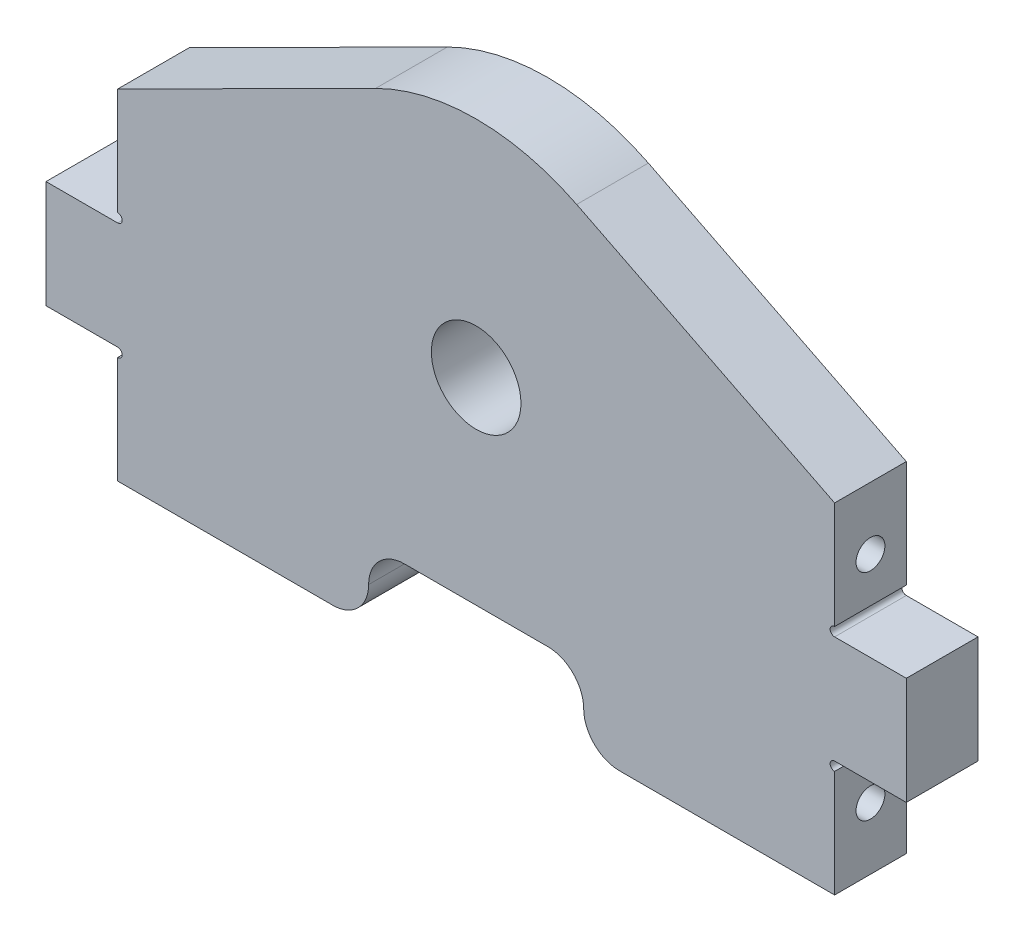
SolidWorks part; units mm, degrees
material "6061-T6 (SS)"
ref_plane "Front Plane" through (0, 0, 0) normal (0, 0, 1) x (1, 0, 0)
ref_plane "Top Plane" through (0, 0, 0) normal (0, 1, 0) x (1, 0, 0)
ref_plane "Right Plane" through (0, 0, 0) normal (1, 0, 0) x (0, 0, -1)
sketch "Sketch1" plane through (0, 0, 0) normal (0, 0, 1) x (1, 0, 0)
  line L1 (-63.5, 0) -> (63.5, 0)
  line L2 (-63.5, 0) -> (-63.5, 152.4)
  line L3 (-63.5, 152.4) -> (63.5, 152.4)
  line L4 (63.5, 0) -> (63.5, 152.4)
  dimension "D1" = 127
  dimension "D2" = 152.4
extrude "Boss-Extrude1" add sketch "Sketch1" along normal blind 12.7
sketch "Sketch2" plane through (0, 0, 12.7) normal (0, 0, 1) x (1, 0, 0)
  line L0 (-63.5, 56.977) -> (-17.8077, 79.9181)
  line L1 (-63.5, 152.4) -> (-63.5, 0) construction
  line L2 (-76.2, 56.977) -> (-63.5, 56.977) construction
  line L3 (63.5, 56.977) -> (17.8077, 79.9181)
  line L4 (63.5, 0) -> (63.5, 152.4) construction
  line L5 (63.5, 56.977) -> (76.2, 56.977) construction
  line L6 (-63.5, 56.977) -> (-63.5, 152.4)
  line L7 (-63.5, 152.4) -> (63.5, 152.4)
  line L8 (63.5, 152.4) -> (63.5, 56.977)
  circle A0 centre (0, 44.45) radius 7.9375
  circle A1 centre (0, 44.45) radius 39.6875
  line M1 (-63.5, 152.4) -> (-63.5, 0)
  line M3 (63.5, 0) -> (63.5, 152.4)
  line M4 (63.5, 152.4) -> (-63.5, 152.4)
  dimension "D1" = 79.375
extrude "Cut-Extrude1" cut sketch "Sketch2" against normal through all contours A1 L3 L0 M3 M4 M1 | A0 region at (0, 111.9722, 12.7) region at (0, 44.45, 12.7)
sketch "Sketch3" plane through (0, 0, 0) normal (0, 0, -1) x (-1, 0, 0)
  line L1 (-63.5, 0) -> (63.5, 0)
  line L2 (-63.5, 0) -> (-63.5, -3.175)
  line L3 (-63.5, -3.175) -> (63.5, -3.175)
  line L4 (63.5, 0) -> (63.5, -3.175)
extrude "Boss-Extrude2" add sketch "Sketch3" against normal blind 12.7
sketch "Sketch4" plane through (0, 0, 12.7) normal (0, 0, 1) x (1, 0, 0)
  line L0 (63.5, -3.175) -> (-63.5, -3.175) construction
  line L1 (-19.05, -3.175) -> (19.05, -3.175)
  line L2 (-19.05, -3.175) -> (-19.05, 9.525)
  line L3 (-19.05, 9.525) -> (19.05, 9.525)
  line L4 (19.05, -3.175) -> (19.05, 9.525)
  line L5 (63.5, -3.175) -> (63.5, 56.977) construction
  line L6 (-63.5, 56.977) -> (-63.5, -3.175) construction
  dimension "D1" = 44.45
  dimension "D2" = 44.45
  dimension "D3" = 12.7
extrude "Cut-Extrude2" cut sketch "Sketch4" against normal through all
fillet "Fillet1" radius 6.35 4 edges at (-19.05, -3.175, 6.35) (-19.05, 9.525, 6.35) (19.05, 9.525, 6.35) (19.05, -3.175, 6.35)
hole_wizard "1/4-20 Tapped Hole1" positions "Sketch6" profile "Sketch5" tap size "1/4-20" standard "ANSI Inch"
sketch "Sketch6" plane through (63.5, 0, 0) normal (1, 0, 0) x (0, 0, -1)
  line L0 (0, 26.901) -> (-6.35, 26.901) construction
  line L1 (0, -3.175) -> (0, 56.977) construction
  line L2 (-6.35, 26.901) -> (-6.35, 45.951) construction
  line L3 (-6.35, 45.951) -> (-6.35, 56.977) construction
  line L4 (0, 56.977) -> (-12.7, 56.977) construction
  line L5 (-6.35, 56.977) -> (-12.7, 26.901) construction
  line L6 (-12.7, -3.175) -> (-12.7, 56.977) construction
  line L7 (-12.7, 26.901) -> (-6.35, -3.175) construction
  line L8 (-12.7, -3.175) -> (0, -3.175) construction
  line L9 (-6.35, -3.175) -> (-6.35, 7.851) construction
  line L10 (-6.35, 7.851) -> (-6.35, 26.901) construction
  point P6 (-6.35, 45.951)
  point P20 (-6.35, 7.851)
  dimension "D1" = 19.05
sketch "Sketch5" plane through (63.5, 45.951, 6.35) normal (0, 1, 0) x (0, 0, -1)
  line L0 (0, 0) -> (0, 18.0438)
  line L1 (0, 18.0438) -> (2.5527, 16.51)
  line L2 (2.5527, 16.51) -> (2.5527, 0)
  line L5 (2.5527, 0) -> (0, 0)
  line L10 (0, 18.0438) -> (-2.5527, 16.51) construction
  line L11 (0, -6.35) -> (0, 107.95) construction
  dimension "Tap Drill Dia." = 5.1054
  dimension "Tap Drill Depth" = 16.51
  dimension "Drill Angle" = 118
sketch "Sketch7" plane through (63.5, 0, 0) normal (1, 0, 0) x (0, 0, -1)
  line L0 (-12.7, -3.175) -> (-12.7, 56.977) construction
  line L1 (-12.7, 17.376) -> (0, 17.376)
  line L2 (-12.7, 17.376) -> (-12.7, 36.426)
  line L3 (-12.7, 36.426) -> (0, 36.426)
  line L4 (0, 17.376) -> (0, 36.426)
  line L5 (0, -3.175) -> (0, 56.977) construction
  point P8 (0, 26.901)
  dimension "D1" = 19.05
extrude "Boss-Extrude3" add sketch "Sketch7" along normal blind 12.7
sketch "Sketch8" plane through (0, 0, 12.7) normal (0, 0, 1) x (1, 0, 0)
  line L0 (63.5, 36.426) -> (63.5, 56.977) construction
  line L1 (63.5, -3.175) -> (63.5, 17.376) construction
  circle A0 centre (63.5, 37.2198) radius 0.7937
  circle A1 centre (63.5, 16.5823) radius 0.7937
  dimension "D1" = 1.5875
extrude "Cut-Extrude3" cut sketch "Sketch8" against normal through all
mirror "Mirror1" about plane through (0, 0, 0) normal (1, 0, 0) of "1/4-20 Tapped Hole1", "Boss-Extrude3", "Cut-Extrude3"
